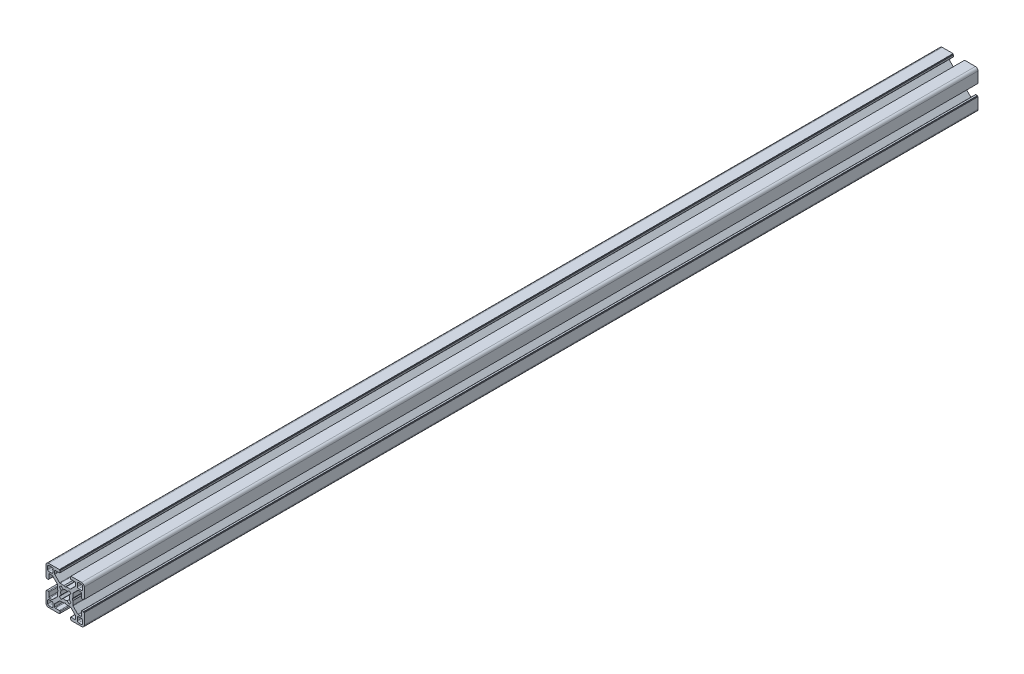
SolidWorks part; units mm, degrees
ref_plane "Front Plane" through (0, 0, 0) normal (0, 0, 1) x (1, 0, 0)
ref_plane "Top Plane" through (0, 0, 0) normal (0, 1, 0) x (1, 0, 0)
ref_plane "Right Plane" through (0, 0, 0) normal (1, 0, 0) x (0, 0, -1)
sketch "Sketch1" plane through (0, 0, 0) normal (0, 0, 1) x (1, 0, 0)
  line L0 (-15, 0) -> (15, 0) construction
  line L1 (0, -15) -> (0, 15) construction
  line L2 (-4.5, 15) -> (4.5, 15) construction
  line L3 (-4, -15) -> (4, -15) construction
  line L4 (-4.5, 15) -> (-4.5, 14.5)
  line L5 (-4.5, 14.5) -> (-4, 14.5)
  line L6 (-4, 14.5) -> (-4, 13.29)
  line L7 (-4.5, 12.79) -> (-7.7675, 12.79)
  line L8 (-8.2675, 12.29) -> (-8.2675, 10.2707)
  line L9 (-8.1211, 9.9171) -> (-4.3504, 6.1464)
  line L10 (-3.9968, 6) -> (0, 6)
  line L11 (0, 0) -> (-15, 15) construction
  line L12 (-4.5, 15) -> (-12.968, 15)
  line L14 (-12.705, 9.5135) -> (-10.5135, 9.5135)
  line L15 (-13.705, 10.5135) -> (-13.705, 12.705)
  line L16 (-12.705, 13.705) -> (-10.5135, 13.705)
  line L17 (-9.5135, 10.5135) -> (-9.5135, 12.705)
  line L18 (-13.705, 9.5135) -> (-9.5135, 13.705) construction
  line L19 (-13.705, 13.705) -> (-9.5135, 9.5135) construction
  line L20 (-3.1568, 4.5038) -> (-1.5303, 3.1477) construction
  line L21 (-4.5038, 3.1568) -> (-3.1477, 1.5303) construction
  line L22 (-6, 3.9968) -> (-6, 0)
  line L23 (-9.9171, 8.1211) -> (-6.1464, 4.3504)
  line L24 (-15, 4.5) -> (-15, 12.968)
  line L25 (-12.29, 8.2675) -> (-10.2707, 8.2675)
  line L26 (-12.79, 4.5) -> (-12.79, 7.7675)
  line L27 (-14.5, 4) -> (-13.29, 4)
  line L28 (-14.5, 4.5) -> (-14.5, 4)
  line L29 (-15, 4.5) -> (-14.5, 4.5)
  circle A0 centre (0, 0) radius 3.5
  arc A1 (-12.968, 15) -> (-15, 12.968) centre (-12.968, 12.968) ccw
  circle A2 centre (0, 0) radius 5.5 construction
  arc A3 (-10.5135, 9.5135) -> (-9.5135, 10.5135) centre (-10.5135, 10.5135) ccw
  arc A4 (-13.705, 12.705) -> (-12.705, 13.705) centre (-12.705, 12.705) cw
  arc A5 (-10.5135, 13.705) -> (-9.5135, 12.705) centre (-10.5135, 12.705) cw
  arc A6 (-12.705, 9.5135) -> (-13.705, 10.5135) centre (-12.705, 10.5135) cw
  arc A7 (-12.79, 4.5) -> (-13.29, 4) centre (-13.29, 4.5) cw
  arc A8 (-12.29, 8.2675) -> (-12.79, 7.7675) centre (-12.29, 7.7675) ccw
  arc A9 (-9.9171, 8.1211) -> (-10.2707, 8.2675) centre (-10.2707, 7.7675) ccw
  arc A10 (-6, 3.9968) -> (-6.1464, 4.3504) centre (-6.5, 3.9968) ccw
  arc A11 (-4.3504, 6.1464) -> (-3.9968, 6) centre (-3.9968, 6.5) ccw
  arc A12 (-4, 13.29) -> (-4.5, 12.79) centre (-4.5, 13.29) cw
  arc A13 (-7.7675, 12.79) -> (-8.2675, 12.29) centre (-7.7675, 12.29) ccw
  arc A14 (-8.2675, 10.2707) -> (-8.1211, 9.9171) centre (-7.7675, 10.2707) ccw
  point P4 (0, 0)
  point P8 (0, 0)
  point P13 (0, 15)
  point P15 (0, -15)
  point P16 (0, 6)
  point P23 (-11.6092, 11.6093)
  point P26 (0, 6)
  point P62 (-12.79, 4)
  point P65 (-12.79, 8.2675)
  point P68 (-10.0636, 8.2675)
  point P71 (-6, 4.2039)
  point P74 (-4.2039, 6)
  point P77 (-4, 12.79)
  point P80 (-8.2675, 12.79)
  point P83 (-8.2675, 10.0636)
  dimension "Center Hole Diameter" = 7
  dimension "D11" = 2.032
  dimension "D9" = 11
  dimension "D13" = 1
  dimension "D14" = 0.5
  dimension "Rail Height" = 30
  dimension "Rail Width" = 30
  dimension "T-Slot Width" = 8
  dimension "T-Slot Depth" = 9
  dimension "D1" = 9
  dimension "D2" = 45
  dimension "D3" = 8
  dimension "D4" = 2.21
  dimension "D5" = 16.535
  dimension "D7" = 2.54
  dimension "D6" = 1.295
  dimension "D8" = 1.246
  dimension "D10" = 10.36
  dimension "D12" = 1.905
sketch "Sketch2" plane through (0, 0, 0) normal (1, 0, 0) x (0, 0, -1)
  line L0 (-76.2, 0) -> (76.2, 0) construction
  line L2 (0, -15) -> (0, 15) construction
  line L3 (0, -15) -> (0, 15) construction
  line L4 (-76.2, -15) -> (-76.2, 15) construction
  line L5 (76.2, -15) -> (76.2, 15) construction
  point P0 (-38.7, 0)
  point P3 (0, 0)
  point P4 (38.7, 0)
  point P12 (-76.2, 0)
  point P14 (76.2, 0)
  dimension "Length" = 152.4
  dimension "D1" = 37.5
sketch "Sketch3" plane through (0, 0, 0) normal (0, 0, 1) x (1, 0, 0)
  line L0 (-4.5038, 3.1568) -> (-3.1477, 1.5303)
  line L1 (0, 3.5) -> (0, 5.5)
  line L2 (-5.5, 0) -> (-3.5, 0)
  line L7 (-6, 3.9968) -> (-6, 0) construction
  line L31 (-9.9171, 8.1211) -> (-6.1464, 4.3504) construction
  line L117 (-12.29, 8.2675) -> (-10.2707, 8.2675) construction
  line L118 (-12.79, 4.5) -> (-12.79, 7.7675) construction
  line L157 (-12.705, 9.5135) -> (-10.5135, 9.5135)
  line L158 (-9.5135, 10.5135) -> (-9.5135, 12.705)
  line L163 (-10.5135, 13.705) -> (-12.705, 13.705)
  line L164 (-13.705, 12.705) -> (-13.705, 10.5135)
  line L165 (-12.705, 9.5135) -> (-10.5135, 9.5135)
  line L166 (-9.5135, 10.5135) -> (-9.5135, 12.705)
  line L167 (-10.5135, 13.705) -> (-12.705, 13.705)
  line L168 (-13.705, 12.705) -> (-13.705, 10.5135)
  line L169 (-14.5, 4) -> (-13.29, 4) construction
  line L170 (-14.5, 4.5) -> (-14.5, 4) construction
  line L171 (-15, 4.5) -> (-14.5, 4.5) construction
  line L172 (-15, 4.5) -> (-15, 12.968) construction
  line L173 (-4.5, 15) -> (-12.968, 15) construction
  line L174 (-4.5, 15) -> (-4.5, 14.5) construction
  line L175 (-4.5, 14.5) -> (-4, 14.5) construction
  line L176 (-4, 14.5) -> (-4, 13.29) construction
  line L177 (-4.5, 12.79) -> (-7.7675, 12.79) construction
  line L178 (-8.2675, 12.29) -> (-8.2675, 10.2707) construction
  line L179 (-8.1211, 9.9171) -> (-4.3504, 6.1464) construction
  line L180 (-3.9968, 6) -> (0, 6) construction
  line L181 (-6, 3.9968) -> (-6, 0.866)
  line L182 (-9.9171, 8.1211) -> (-6.1464, 4.3504)
  line L183 (-12.29, 8.2675) -> (-10.2707, 8.2675)
  line L184 (-12.79, 4.5) -> (-12.79, 7.7675)
  line L185 (-14.5, 4) -> (-13.29, 4)
  line L186 (-14.5, 4.5) -> (-14.5, 4)
  line L187 (-15, 4.5) -> (-14.5, 4.5)
  line L188 (-15, 4.5) -> (-15, 12.968)
  line L189 (-4.5, 15) -> (-12.968, 15)
  line L190 (-4.5, 15) -> (-4.5, 14.5)
  line L191 (-4.5, 14.5) -> (-4, 14.5)
  line L192 (-4, 14.5) -> (-4, 13.29)
  line L193 (-4.5, 12.79) -> (-7.7675, 12.79)
  line L194 (-8.2675, 12.29) -> (-8.2675, 10.2707)
  line L195 (-8.1211, 9.9171) -> (-4.3504, 6.1464)
  line L196 (-3.9968, 6) -> (-0.866, 6)
  line L197 (-0.866, 6) -> (0, 5.5)
  line L198 (0, -15) -> (0, 15) construction
  line L199 (0, 0) -> (-15, 15) construction
  line L200 (0, 0) -> (-15, 15) construction
  line L201 (-3.1568, 4.5038) -> (-1.5303, 3.1477) construction
  line L202 (-3.1568, 4.5038) -> (-1.5303, 3.1477)
  line L203 (-6, 0.866) -> (-5.5, 0)
  line L204 (-15, 0) -> (15, 0) construction
  line L205 (-15, 0) -> (15, 0) construction
  line L206 (0, -15) -> (0, 15) construction
  arc A0 (-3.5, 0) -> (-3.1477, 1.5303) centre (0, 0) cw
  arc A10 (-6, 3.9968) -> (-6.1464, 4.3504) centre (-6.5, 3.9968) ccw construction
  circle A16 centre (0, 0) radius 3.5
  arc A18 (0, 3.5) -> (-1.5303, 3.1477) centre (0, 0) ccw
  arc A20 (-9.9171, 8.1211) -> (-10.2707, 8.2675) centre (-10.2707, 7.7675) ccw construction
  arc A22 (-12.29, 8.2675) -> (-12.79, 7.7675) centre (-12.29, 7.7675) ccw construction
  arc A28 (-13.29, 4) -> (-12.79, 4.5) centre (-13.29, 4.5) ccw construction
  arc A29 (-10.5135, 9.5135) -> (-9.5135, 10.5135) centre (-10.5135, 10.5135) ccw
  arc A30 (-9.5135, 12.705) -> (-10.5135, 13.705) centre (-10.5135, 12.705) ccw
  arc A31 (-12.705, 13.705) -> (-13.705, 12.705) centre (-12.705, 12.705) ccw
  arc A32 (-13.705, 10.5135) -> (-12.705, 9.5135) centre (-12.705, 10.5135) ccw
  arc A33 (-10.5135, 9.5135) -> (-9.5135, 10.5135) centre (-10.5135, 10.5135) ccw
  arc A34 (-9.5135, 12.705) -> (-10.5135, 13.705) centre (-10.5135, 12.705) ccw
  arc A35 (-12.705, 13.705) -> (-13.705, 12.705) centre (-12.705, 12.705) ccw
  arc A36 (-13.705, 10.5135) -> (-12.705, 9.5135) centre (-12.705, 10.5135) ccw
  arc A37 (-12.968, 15) -> (-15, 12.968) centre (-12.968, 12.968) ccw construction
  arc A38 (-4.5, 12.79) -> (-4, 13.29) centre (-4.5, 13.29) ccw construction
  arc A39 (-7.7675, 12.79) -> (-8.2675, 12.29) centre (-7.7675, 12.29) ccw construction
  arc A40 (-8.2675, 10.2707) -> (-8.1211, 9.9171) centre (-7.7675, 10.2707) ccw construction
  arc A41 (-4.3504, 6.1464) -> (-3.9968, 6) centre (-3.9968, 6.5) ccw construction
  arc A42 (-6, 3.9968) -> (-6.1464, 4.3504) centre (-6.5, 3.9968) ccw
  arc A43 (-9.9171, 8.1211) -> (-10.2707, 8.2675) centre (-10.2707, 7.7675) ccw
  arc A44 (-12.29, 8.2675) -> (-12.79, 7.7675) centre (-12.29, 7.7675) ccw
  arc A45 (-13.29, 4) -> (-12.79, 4.5) centre (-13.29, 4.5) ccw
  arc A46 (-12.968, 15) -> (-15, 12.968) centre (-12.968, 12.968) ccw
  arc A47 (-4.5, 12.79) -> (-4, 13.29) centre (-4.5, 13.29) ccw
  arc A48 (-7.7675, 12.79) -> (-8.2675, 12.29) centre (-7.7675, 12.29) ccw
  arc A49 (-8.2675, 10.2707) -> (-8.1211, 9.9171) centre (-7.7675, 10.2707) ccw
  arc A50 (-4.3504, 6.1464) -> (-3.9968, 6) centre (-3.9968, 6.5) ccw
  circle A51 centre (0, 0) radius 5.5 construction
  arc A52 (-3.1568, 4.5038) -> (-4.5038, 3.1568) centre (0, 0) ccw
  dimension "D3" = 60
  dimension "D4" = 60
  dimension "D1" = 0
  dimension "D2" = 0
extrude "Boss-Extrude1" add sketch "Sketch3" along normal mid plane 700
pattern_circular "CirPattern1" count 4 over 360 about axis through (0, 0, 76.2) along (0, 0, -1) of "Boss-Extrude1"
ref_plane "Contact Plane1" through (15, 0, 0) normal (1, 0, 0) x (0, 0, -1)
ref_plane "Contact Plane2" through (0, -15, 0) normal (0, 1, 0) x (1, 0, 0)
ref_plane "Contact Plane3" through (-15, 0, 0) normal (1, 0, 0) x (0, 0, -1)
ref_plane "Contact Plane4" through (0, 15, 0) normal (0, 1, 0) x (1, 0, 0)
equation "\"D1@Sketch2\" = \"Rail Height@Sketch1\" * 1.25"
equation "\"D1@Sketch1\"=\"T-Slot Width@Sketch1\"+1mm"
equation "\"D3@Sketch1\"=\"T-Slot Width@Sketch1\""
equation "\"D1@Boss-Extrude1\"=\"length\""
equation "\"length\"= 700"
